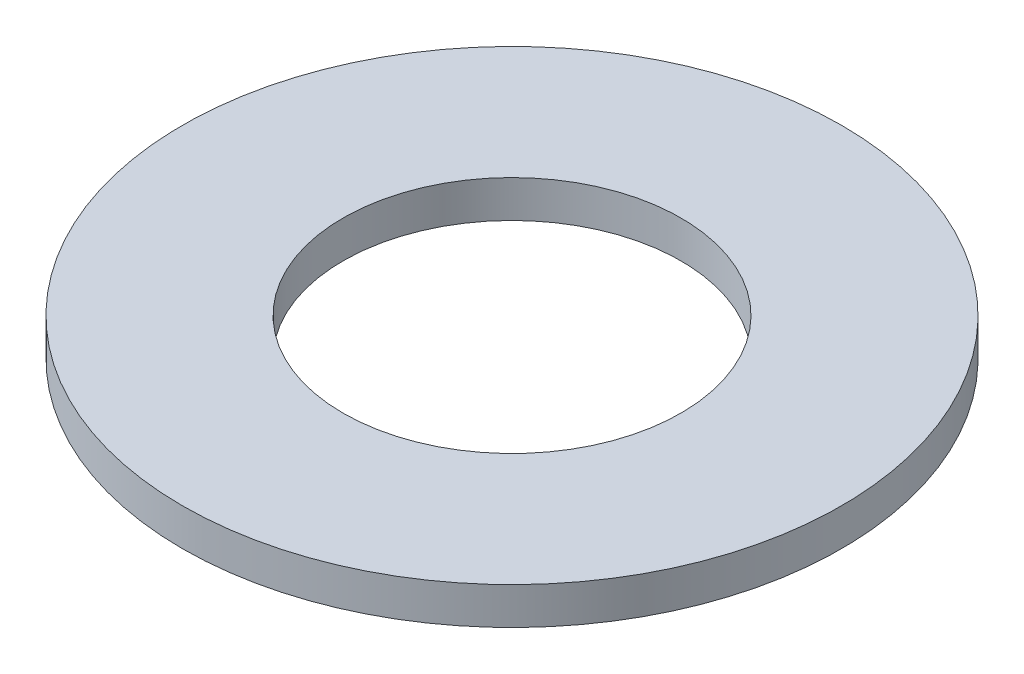
SolidWorks part; units mm, degrees
ref_plane "Front Plane" through (0, 0, 0) normal (0, 0, 1) x (1, 0, 0)
ref_plane "Top Plane" through (0, 0, 0) normal (0, 1, 0) x (1, 0, 0)
ref_plane "Right Plane" through (0, 0, 0) normal (1, 0, 0) x (0, 0, -1)
sketch "Sketch1" plane through (0, 0, 0) normal (0, 1, 0) x (1, 0, 0)
  circle A0 centre (0, 0) radius 97.5
  dimension "FLANGE_OD" = 195
extrude "Boss-Extrude1" add sketch "Sketch1" along normal blind 11
sketch "Sketch2" plane through (0, 0, 0) normal (0, 1, 0) x (1, 0, 0)
  circle A0 centre (0, 0) radius 50
  dimension "BORE_D" = 100
extrude "Cut-Extrude1" cut sketch "Sketch2" along normal through all
sketch "Sketch3" plane through (0, 11, 0) normal (0, 1, 0) x (1, 0, 0)
  circle A0 centre (0, 0) radius 36.0843 construction
  circle A1 centre (-36.0843, 0) radius 6.8457
  dimension "BOLT_D" = 13.6913
  dimension "BOLT_PCD" = 72.1686
extrude "Cut-Extrude2" cut sketch "Sketch3" against normal blind 10.1211 rebuild error yes
pattern_circular "CirPattern1" count 3 over 360 rebuild error yes
